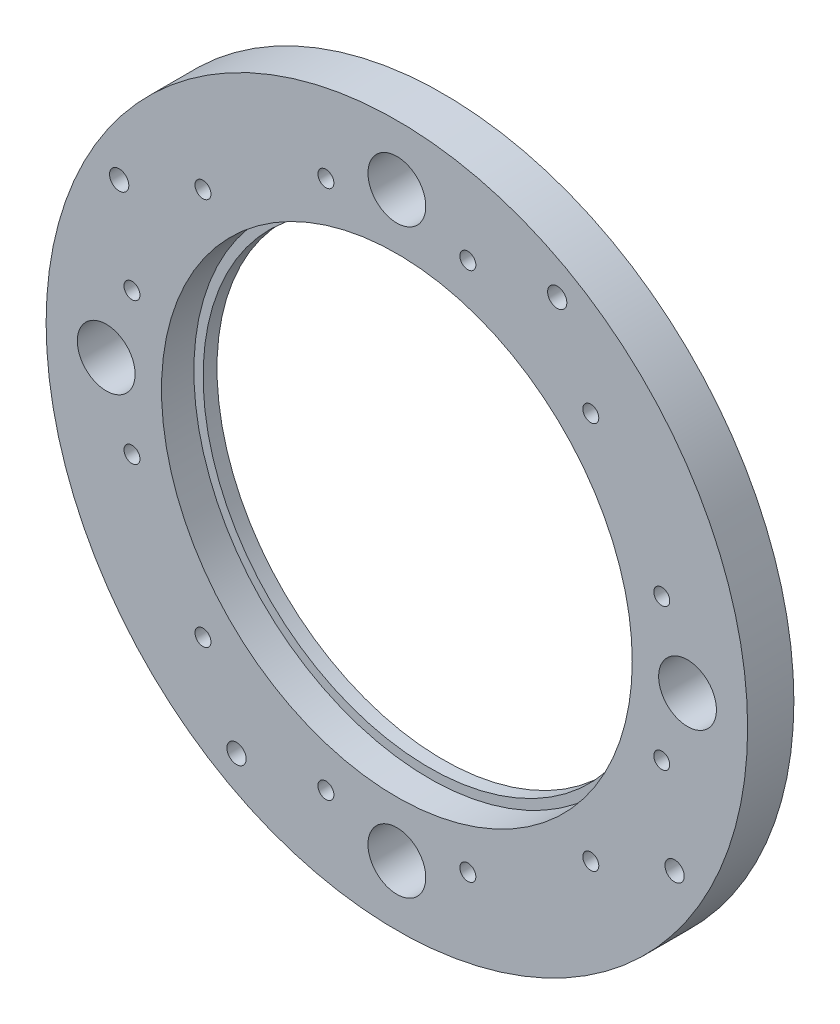
SolidWorks part; units mm, degrees
material "6061 Alloy"
ref_plane "Front Plane" through (0, 0, 0) normal (0, 0, 1) x (1, 0, 0)
ref_plane "Top Plane" through (0, 0, 0) normal (0, 1, 0) x (1, 0, 0)
ref_plane "Right Plane" through (0, 0, 0) normal (1, 0, 0) x (0, 0, -1)
ref_plane "Plane1" through (0, 0, 0) normal (0, -1, 0) x (1, 0, 0)
sketch "Sketch1" plane through (0, 0, 0) normal (0, -1, 0) x (1, 0, 0)
  line L0 (75.85, 5) -> (0, 5)
  line L1 (0, 5) -> (0, -5)
  line L2 (0, -5) -> (75.85, -5)
  line L3 (75.85, -5) -> (75.85, 5)
  line L4 (0, 5) -> (0, -5) construction
revolve "Revolve1" add sketch "Sketch1" angle 360 about L4 reverse direction yes
hole_wizard "M3.5 Clearance Hole1" positions "Sketch3" profile "Sketch2" hole size "M3.5" standard "ANSI Metric"
sketch "Sketch3" plane through (0, 0, -5) normal (0, 0, -1) x (-1, 0, 0)
  point P0 (60.0519, 34.671)
  point P1 (-34.671, 60.0519)
  point P2 (-60.0519, -34.671)
  point P3 (34.671, -60.0519)
sketch "Sketch2" plane through (-60.0519, 34.671, -5) normal (1, 0, 0) x (0, 1, 0)
  line L0 (0, 0) -> (0, 10)
  line L1 (0, 10) -> (2.0828, 10)
  line L2 (2.0828, 10) -> (2.0828, 0)
  line L5 (2.0828, 0) -> (0, 0)
  line L11 (0, -6.35) -> (0, 107.95) construction
  dimension "Thru Hole Dia." = 4.1656
  dimension "Thru Hole Depth" = 10
hole_wizard "M3 Clearance Hole1" positions "Sketch5" profile "Sketch4" hole size "M3" standard "ANSI Metric"
sketch "Sketch5" plane through (0, 0, -5) normal (0, 0, -1) x (-1, 0, 0)
  point P0 (41.9314, 41.9314)
  point P1 (57.2794, 15.348)
  point P2 (57.2794, -15.348)
  point P3 (41.9314, -41.9314)
  point P4 (15.348, -57.2794)
  point P5 (-15.348, -57.2794)
  point P6 (-41.9314, -41.9314)
  point P7 (-57.2794, -15.348)
  point P8 (-57.2794, 15.348)
  point P9 (-41.9314, 41.9314)
  point P10 (-15.348, 57.2794)
  point P11 (15.348, 57.2794)
sketch "Sketch4" plane through (-41.9314, 41.9314, -5) normal (1, 0, 0) x (0, 1, 0)
  line L0 (0, 0) -> (0, 10)
  line L1 (0, 10) -> (1.7272, 10)
  line L2 (1.7272, 10) -> (1.7272, 0)
  line L5 (1.7272, 0) -> (0, 0)
  line L11 (0, -6.35) -> (0, 107.95) construction
  dimension "Thru Hole Dia." = 3.4544
  dimension "Thru Hole Depth" = 10
hole_wizard "Ø12.5 (12.5) Diameter Hole1" positions "Sketch7" profile "Sketch6" hole size "Ø12.5" standard "ANSI Metric"
sketch "Sketch7" plane through (0, 0, -5) normal (0, 0, -1) x (-1, 0, 0)
  point P0 (62.85, 0)
  point P1 (0, -62.85)
  point P2 (-62.85, 0)
  point P3 (0, 62.85)
sketch "Sketch6" plane through (-62.85, 0, -5) normal (1, 0, 0) x (0, 1, 0)
  line L0 (0, 0) -> (0, 10)
  line L1 (0, 10) -> (6.25, 10)
  line L2 (6.25, 10) -> (6.25, 0)
  line L5 (6.25, 0) -> (0, 0)
  line L11 (0, -6.35) -> (0, 107.95) construction
  dimension "Thru Hole Dia." = 12.5
  dimension "Thru Hole Depth" = 10
hole_wizard "CBORE for M90 Hex Head Bolt1" positions "Sketch9" profile "Sketch8" counterbore size "M90" standard "ANSI Metric"
sketch "Sketch9" plane through (0, 0, 5) normal (0, 0, 1) x (1, 0, 0)
  point P0 (0, 0)
sketch "Sketch8" plane through (0, 0, 5) normal (1, 0, 0) x (0, -1, 0)
  line L0 (0, 0) -> (0, 10)
  line L1 (0, 10) -> (48.9, 10)
  line L3 (48.9, 10) -> (48.9, 7)
  line L4 (48.9, 7) -> (50.9, 7)
  line L5 (50.9, 7) -> (50.9, 0)
  line L7 (50.9, 0) -> (0, 0)
  line L11 (0, -6.35) -> (0, 107.95) construction
  dimension "Thru Hole Dia." = 97.8
  dimension "Thru Hole Depth" = 10
  dimension "C'Bore Dia." = 101.8
  dimension "C'Bore Depth" = 7
